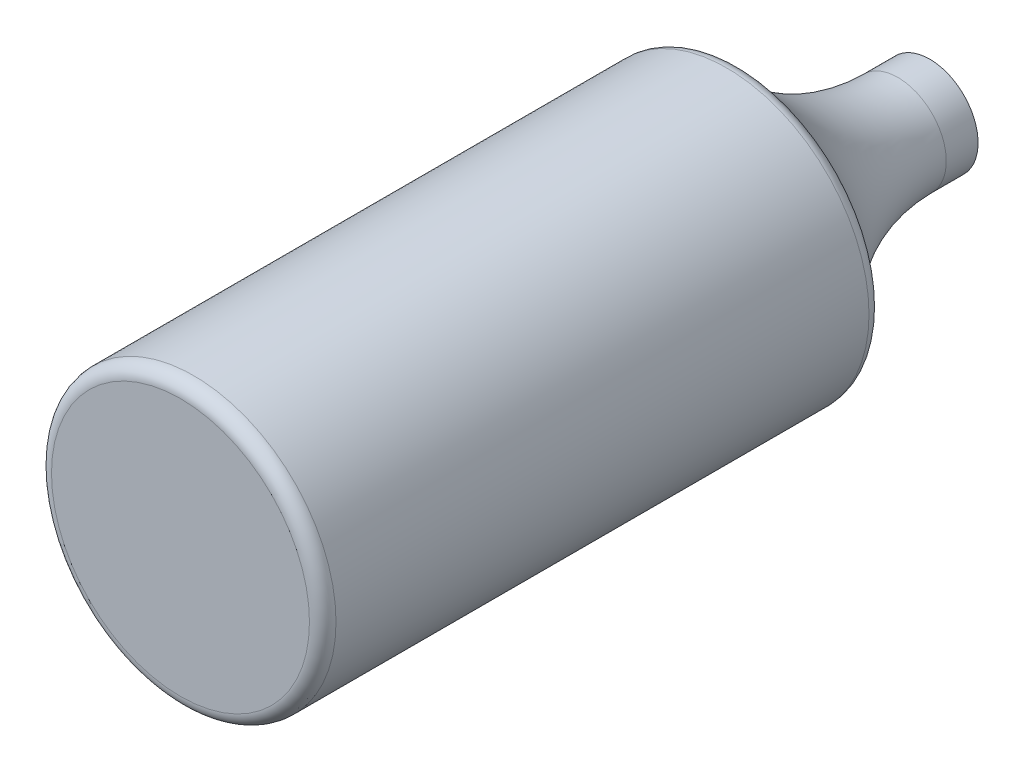
SolidWorks part; units mm, degrees
ref_plane "Front Plane" through (0, 0, 0) normal (0, 0, 1) x (1, 0, 0)
ref_plane "Top Plane" through (0, 0, 0) normal (0, 1, 0) x (1, 0, 0)
ref_plane "Right Plane" through (0, 0, 0) normal (1, 0, 0) x (0, 0, -1)
sketch "Sketch1" plane through (0, 0, 0) normal (0, 0, 1) x (1, 0, 0)
  circle A0 centre (0, 0) radius 7.5
  dimension "D1" = 15
extrude "Boss-Extrude1" add sketch "Sketch1" along normal blind 29.5
sketch "Sketch2" plane through (0, 0, 0) normal (0, 0, -1) x (-1, 0, 0)
  circle A0 centre (0, 0) radius 2.55
  dimension "D1" = 5.1
extrude "Boss-Extrude2" add sketch "Sketch2" along normal blind 10
fillet "Fillet1" radius 0.7 2 edges at (7.5, 0, 0) (7.5, 0, 29.5)
fillet "Fillet2" radius 10 1 edges at (-2.55, 0, 0)
